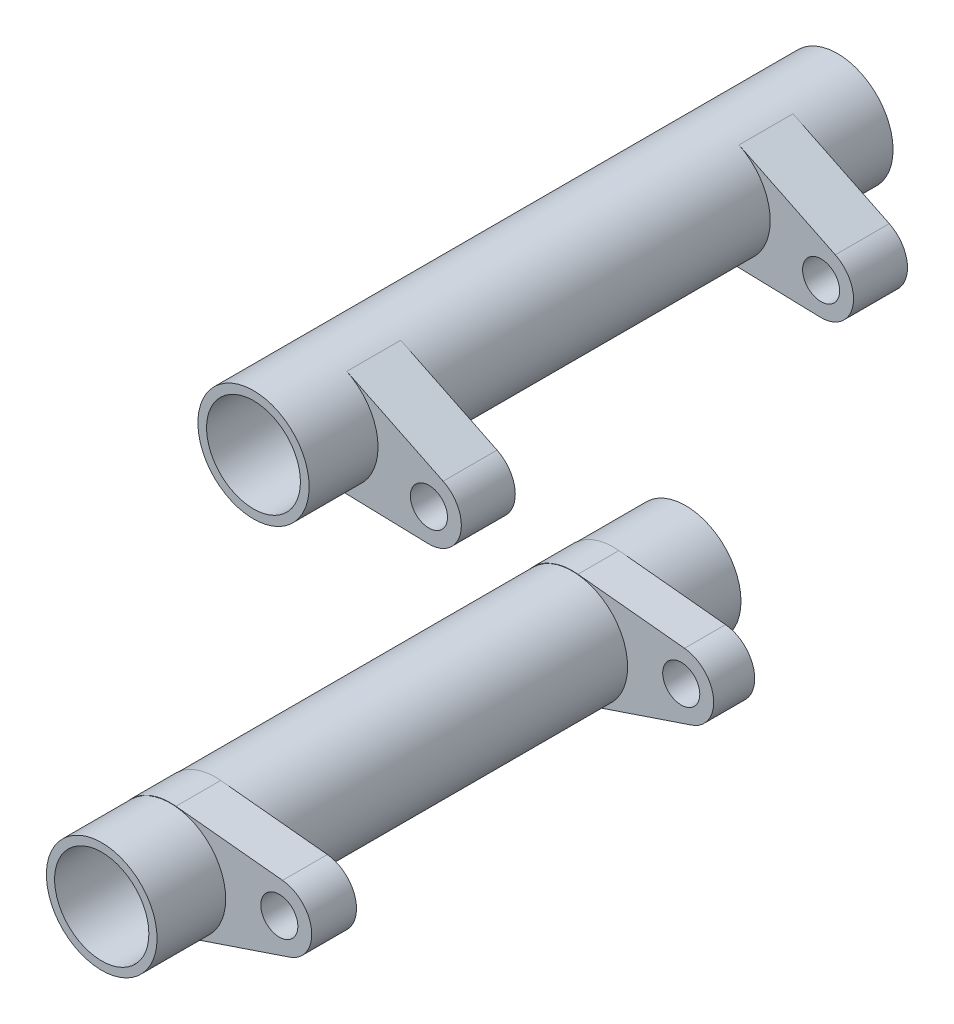
SolidWorks part; units mm, degrees
material "Stainless Steel (ferritic)"
ref_plane "Front Plane" through (0, 0, 0) normal (0, 0, 1) x (1, 0, 0)
ref_plane "Top Plane" through (0, 0, 0) normal (0, 1, 0) x (1, 0, 0)
ref_plane "Right Plane" through (0, 0, 0) normal (1, 0, 0) x (0, 0, -1)
sketch "Sketch1" plane through (0, 0, 0) normal (0, 0, 1) x (1, 0, 0)
  line L0 (0, 0) -> (12.9968, 40) construction
  line L1 (12.9968, 40) -> (0, 40) construction
  line L2 (0, 40) -> (0, 0) construction
  line L3 (12.8661, 35.2393) -> (24.5081, 34.9197) construction
  line L4 (24.5081, 34.9197) -> (25.5522, 39.1756) construction
  line L5 (25.5522, 39.1756) -> (15.0843, 44.2806) construction
  line L6 (1.5216, -4.5129) -> (12.5575, -0.7918) construction
  line L7 (12.5575, -0.7918) -> (12.0675, 3.5628) construction
  line L8 (12.0675, 3.5628) -> (0.4806, 4.7382) construction
  line L9 (12.9968, 40) -> (25.0301, 37.0476) construction
  line L10 (0, 0) -> (12.3125, 1.3855) construction
  line L11 (0.4806, 4.7382) -> (9.6115, 3.812)
  line L12 (10.2183, -1.5806) -> (1.5216, -4.5129)
  line L13 (15.0843, 44.2806) -> (23.3334, 40.2577)
  line L14 (22.0404, 34.9874) -> (12.8661, 35.2393)
  circle A0 centre (0, 0) radius 4.7625 construction
  circle A1 centre (12.9968, 40) radius 4.7625 construction
  circle A2 centre (22.1166, 37.7625) radius 1.5875
  circle A3 centre (9.3314, 1.05) radius 1.5875
  arc A4 (12.8661, 35.2393) -> (15.0843, 44.2806) centre (12.9968, 40) cw
  arc A5 (0.4806, 4.7382) -> (1.5216, -4.5129) centre (0, 0) ccw
  arc A6 (9.6115, 3.812) -> (10.2183, -1.5806) centre (9.3314, 1.05) cw
  arc A7 (22.0404, 34.9874) -> (23.3334, 40.2577) centre (22.1166, 37.7625) ccw
  dimension "D1" = 9.525
  dimension "D7" = 3.175
  dimension "D2" = 18
  dimension "D3" = 40
  dimension "D4" = 4.3822
  dimension "D5" = 3
  dimension "D6" = 3
extrude "Boss-Extrude1" add sketch "Sketch1" along normal blind 25 and the other way blind 25 contours A0 | A0 L6 L7 L8 A3 | A1 | A1 L3 L4 L5 A2 region at (2.5862, 0.291, 0) region at (15.5244, 39.3799, 0)
ref_plane "Plane1" through (12.9968, 0, 0) normal (1, 0, 0) x (0, 0, -1)
sketch "Sketch2" plane through (0, 0, 0) normal (1, 0, 0) x (0, 0, -1)
  line L0 (-35.4146, 0) -> (31.094, 0) construction
  line L1 (0, 40) -> (0, 0) construction
  line L2 (15.2925, 14.549) -> (-15.2925, 14.549)
  line L3 (15.2925, 14.549) -> (15.2925, 4.7382)
  line L4 (15.2925, 4.7382) -> (-15.2925, 4.7382)
  line L5 (-15.2925, 14.549) -> (-15.2925, 4.7382)
  line L6 (15.2925, 14.549) -> (-15.2925, 4.7382) construction
  line L7 (15.2925, 4.7382) -> (-15.2925, 14.549) construction
  line L8 (25, 4.7382) -> (-25, 4.7382) construction
  line L9 (-34.5957, 14.549) -> (-19.1255, 14.549)
  line L10 (-34.5957, 14.549) -> (-34.5957, 4.7382)
  line L11 (-34.5957, 4.7382) -> (-19.1255, 4.7382)
  line L12 (-19.1255, 14.549) -> (-19.1255, 4.7382)
  line L13 (-34.5957, 14.549) -> (-19.1255, 4.7382) construction
  line L14 (-34.5957, 4.7382) -> (-19.1255, 14.549) construction
  line L15 (32.6575, 14.549) -> (18.8056, 14.549)
  line L16 (32.6575, 14.549) -> (32.6575, 4.7382)
  line L17 (32.6575, 4.7382) -> (18.8056, 4.7382)
  line L18 (18.8056, 14.549) -> (18.8056, 4.7382)
  line L19 (32.6575, 14.549) -> (18.8056, 4.7382) construction
  line L20 (32.6575, 4.7382) -> (18.8056, 14.549) construction
  line L21 (0, 4.7625) -> (0, -4.7625) construction
  line L22 (-54.5704, 4.035) -> (54.5704, 4.035)
  line L23 (-54.5704, 4.035) -> (-54.5704, 0)
  line L24 (-54.5704, 0) -> (54.5704, 0)
  line L25 (54.5704, 4.035) -> (54.5704, 0)
  line L26 (-54.5704, 4.035) -> (54.5704, 0) construction
  line L27 (-54.5704, 0) -> (54.5704, 4.035) construction
  point P3 (0, 9.6436)
  point P10 (-26.8606, 9.6436)
  point P15 (25.7315, 9.6436)
  point P22 (0, 2.0175)
sketch "Sketch3" plane through (12.9968, 0, 0) normal (1, 0, 0) x (0, 0, -1)
  line L0 (0, 40) -> (33.6567, 40) construction
  line L1 (0, 44.7625) -> (0, 35.2375) construction
  line L2 (25, 44.7625) -> (-25, 44.7625) construction
  line L3 (14.4815, 59.4717) -> (-14.4815, 59.4717)
  line L4 (14.4815, 59.4717) -> (14.4815, 44.7625)
  line L5 (14.4815, 44.7625) -> (-14.4815, 44.7625)
  line L6 (-14.4815, 59.4717) -> (-14.4815, 44.7625)
  line L7 (14.4815, 59.4717) -> (-14.4815, 44.7625) construction
  line L8 (14.4815, 44.7625) -> (-14.4815, 59.4717) construction
  line L9 (0, 44.7625) -> (0, 35.2393) construction
  line L10 (-30.0153, 59.4717) -> (-19.0996, 59.4717)
  line L11 (-30.0153, 59.4717) -> (-30.0153, 44.7625)
  line L12 (-30.0153, 44.7625) -> (-19.0996, 44.7625)
  line L13 (-19.0996, 59.4717) -> (-19.0996, 44.7625)
  line L14 (-30.0153, 59.4717) -> (-19.0996, 44.7625) construction
  line L15 (-30.0153, 44.7625) -> (-19.0996, 59.4717) construction
  line L16 (29.3489, 59.4717) -> (19.105, 59.4717)
  line L17 (29.3489, 59.4717) -> (29.3489, 44.7625)
  line L18 (29.3489, 44.7625) -> (19.105, 44.7625)
  line L19 (19.105, 59.4717) -> (19.105, 44.7625)
  line L20 (29.3489, 59.4717) -> (19.105, 44.7625) construction
  line L21 (29.3489, 44.7625) -> (19.105, 59.4717) construction
  line L22 (-27.3337, 44.0179) -> (27.3337, 44.0179)
  line L23 (-27.3337, 44.0179) -> (-27.3337, 40)
  line L24 (-27.3337, 40) -> (27.3337, 40)
  line L25 (27.3337, 44.0179) -> (27.3337, 40)
  line L26 (-27.3337, 44.0179) -> (27.3337, 40) construction
  line L27 (-27.3337, 40) -> (27.3337, 44.0179) construction
  point P4 (0, 52.1171)
  point P11 (-24.5575, 52.1171)
  point P16 (24.227, 52.1171)
  point P21 (0, 42.0089)
revolve "Cut-Revolve1" cut sketch "Sketch2" angle 360 about L0
revolve "Cut-Revolve2" cut sketch "Sketch3" angle 360 about L0
